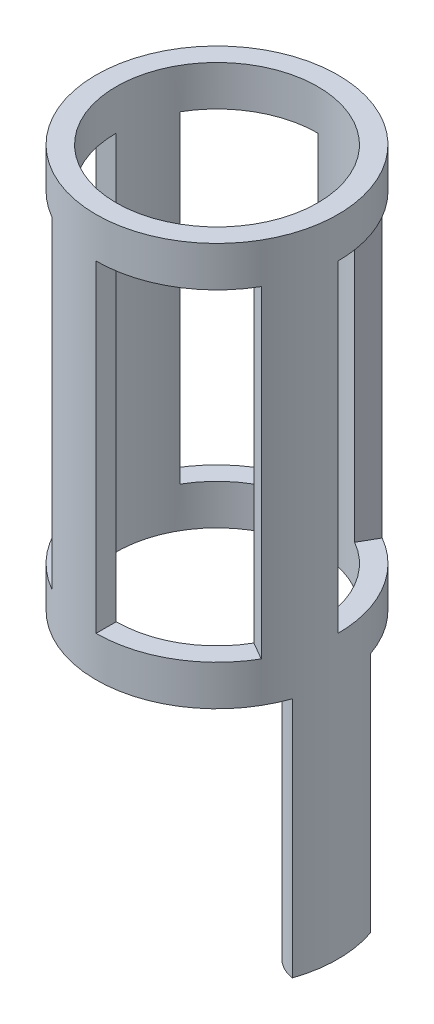
SolidWorks part; units mm, degrees
material "ABS"
ref_plane "Front Plane" through (0, 0, 0) normal (0, 0, 1) x (1, 0, 0)
ref_plane "Top Plane" through (0, 0, 0) normal (0, 1, 0) x (1, 0, 0)
ref_plane "Right Plane" through (0, 0, 0) normal (1, 0, 0) x (0, 0, -1)
sketch "Sketch1" plane through (0, 0, 0) normal (0, 1, 0) x (1, 0, 0)
  line L0 (0, -38.1) -> (0, -31.75)
  line L1 (0, 31.75) -> (0, 38.1)
  line L2 (15.875, 27.4963) -> (19.05, 32.9956)
  line L3 (-15.875, -27.4963) -> (-19.05, -32.9956)
  line L4 (31.75, 0) -> (38.1, 0)
  line L5 (-31.75, 0) -> (-38.1, 0)
  line L6 (27.4963, -15.875) -> (32.9956, -19.05)
  line L7 (-27.4963, 15.875) -> (-32.9956, 19.05)
  circle A0 centre (0, 0) radius 38.1
  circle A1 centre (0, 0) radius 31.75
  dimension "D1" = 76.2
  dimension "D2" = 63.5
  dimension "D3" = 30
  dimension "D4" = 30
extrude "Boss-Extrude1" add sketch "Sketch1" along normal blind 12.7 contours A1 L5 A0 L3 | A1 L7 A0 L5 | A1 L1 A0 L7 | A1 L3 A0 L0 | A1 L0 A0 L6 | A1 L6 A0 L4 | A1 L4 A0 L2 | A1 L2 A0 L1 region at (-8.961, 0, 33.4428) region at (16.7214, 0, 28.9623) region at (-28.9623, 0, 16.7214) region at (33.4428, 0, 8.961) region at (-33.4428, 0, -8.961) region at (28.9623, 0, -16.7214) region at (-16.7214, 0, -28.9623) region at (8.961, 0, -33.4428)
extrude "Boss-Extrude2" add sketch "Sketch1<3>" along normal blind 127 contours A1 L3 A0 L0 | A1 L6 A0 L4 | A1 L2 A0 L1 | A1 L7 A0 L5 region at (-8.961, 0, 33.4428) region at (33.4428, 0, 8.961) region at (-33.4428, 0, -8.961) region at (8.961, 0, -33.4428)
sketch "Sketch1<3>" plane through (0, 0, 0) normal (0, 1, 0) x (1, 0, 0) same geometry as "Sketch1"
sketch "Sketch2" plane through (0, 127, 0) normal (0, 1, 0) x (1, 0, 0)
  circle A0 centre (0, 0) radius 31.75
  circle A1 centre (0, 0) radius 38.1
  arc A2 (-32.9956, 19.05) -> (-38.1, 0) centre (0, 0) ccw construction
extrude "Boss-Extrude3" add sketch "Sketch2" against normal blind 12.7
sketch "Sketch3" plane through (0, 0, 0) normal (0, -1, 0) x (1, 0, 0)
  circle A0 centre (0, 0) radius 31.75
  circle A1 centre (0, 0) radius 38.1
  circle A2 centre (38.1, 0) radius 12.5
  circle A3 centre (38.1, 0) radius 10
  circle A4 centre (0, 0) radius 35.6
  circle M4 centre (0, 0) radius 31.75
  circle M5 centre (0, 0) radius 38.1
  dimension "D1" = 25
  dimension "D2" = 20
  dimension "D3" = 2.5
extrude "Boss-Extrude4" add sketch "Sketch3" along normal blind 76.2 contours A3 A2 M4 | A3 A4 A2 M4 | A4 A3 A2 M5 | A4 A3 A1 | A4 A2 A3 M5 | A2 A4 A3 M4 region at (28.0787, 0, 0) region at (32.2524, 0, 9.5277) region at (32.2524, 0, -9.5277) region at (35.2112, 0, 10.8488) region at (36.4342, 0, 0) region at (35.2112, 0, -10.8488)
